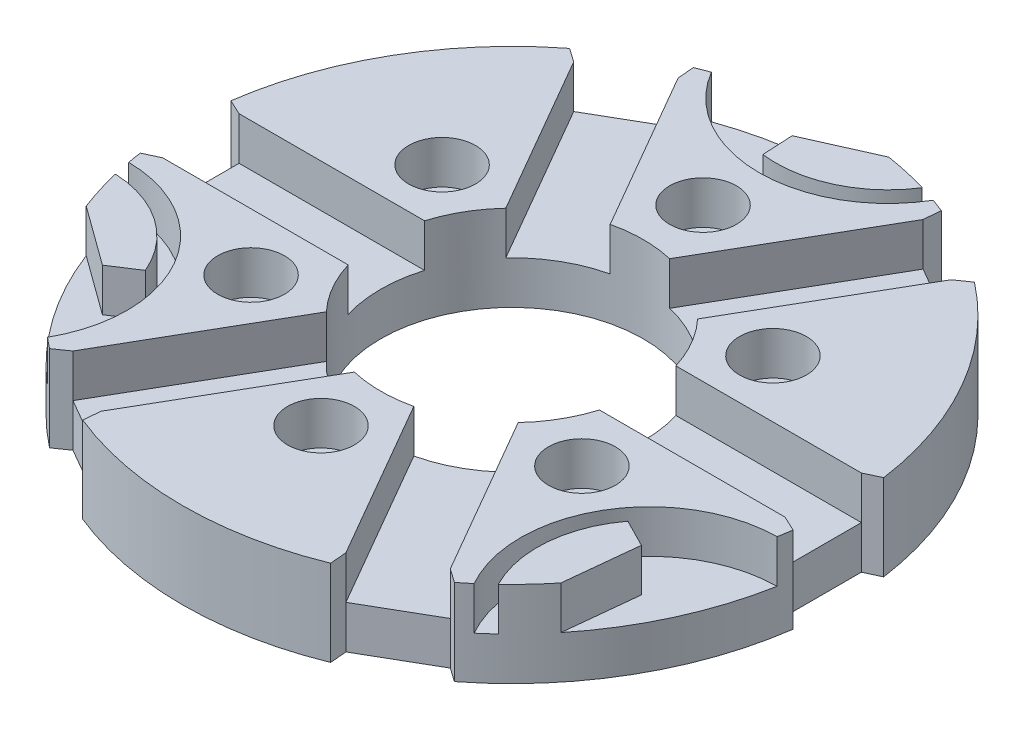
SolidWorks part; units mm, degrees
ref_plane "Front Plane" through (0, 0, 0) normal (0, 0, 1) x (1, 0, 0)
ref_plane "Top Plane" through (0, 0, 0) normal (0, 1, 0) x (1, 0, 0)
ref_plane "Right Plane" through (0, 0, 0) normal (1, 0, 0) x (0, 0, -1)
sketch "Sketch1" plane through (0, 0, 0) normal (0, 1, 0) x (1, 0, 0)
  line L0 (69, 0) -> (-69, 0) construction
  line L1 (0, -69) -> (0, 69) construction
  line L2 (0, 0) -> (34.5, -59.7558) construction
  line L3 (0, 0) -> (59.7558, -34.5) construction
  line L4 (24, -41.5692) -> (26.8492, -74.1354) construction
  line L5 (24, -41.5692) -> (53.9114, -62.5134) construction
  line L6 (29.3432, -66.8239) -> (28.2613, -64.9501)
  line L7 (20.0835, -18.7857) -> (39.5062, -52.4268)
  line L8 (25.6498, -60.4268) -> (25.9565, -63.9317)
  line L9 (39.5062, -52.4268) -> (42.3882, -54.4448)
  line L10 (25.6498, -60.4268) -> (39.5062, -52.4268)
  line L11 (25.6498, -60.4268) -> (6.2271, -26.7857)
  line L12 (-6.2271, -26.7857) -> (-25.6498, -60.4268)
  line L13 (-39.5062, -52.4268) -> (-25.6498, -60.4268)
  line L14 (-39.5062, -52.4268) -> (-20.0835, -18.7857)
  line L15 (0, 0) -> (-34.5, -59.7558) construction
  line L16 (-39.5062, -52.4268) -> (-42.3882, -54.4448)
  line L17 (-25.6498, -60.4268) -> (-25.9565, -63.9317)
  line L18 (-26.3106, -8) -> (-65.1561, -8)
  line L19 (-65.1561, 8) -> (-65.1561, -8)
  line L20 (-65.1561, 8) -> (-26.3106, 8)
  line L21 (0, 0) -> (-69, 0) construction
  line L22 (-65.1561, 8) -> (-68.3447, 9.4869)
  line L23 (-65.1561, -8) -> (-68.3447, -9.4869)
  line L24 (-20.0835, 18.7857) -> (-39.5062, 52.4268)
  line L25 (-25.6498, 60.4268) -> (-39.5062, 52.4268)
  line L26 (-25.6498, 60.4268) -> (-6.2271, 26.7857)
  line L27 (0, 0) -> (-34.5, 59.7558) construction
  line L28 (-25.6498, 60.4268) -> (-25.9565, 63.9317)
  line L29 (-39.5062, 52.4268) -> (-42.3882, 54.4448)
  line L30 (6.2271, 26.7857) -> (25.6498, 60.4268)
  line L31 (39.5062, 52.4268) -> (25.6498, 60.4268)
  line L32 (39.5062, 52.4268) -> (20.0835, 18.7857)
  line L33 (0, 0) -> (34.5, 59.7558) construction
  line L34 (39.5062, 52.4268) -> (42.3882, 54.4448)
  line L35 (25.6498, 60.4268) -> (25.9565, 63.9317)
  line L36 (26.3106, 8) -> (65.1561, 8)
  line L37 (65.1561, -8) -> (65.1561, 8)
  line L38 (65.1561, -8) -> (26.3106, -8)
  line L39 (0, 0) -> (69, 0) construction
  line L40 (65.1561, -8) -> (68.3447, -9.4869)
  line L41 (65.1561, 8) -> (68.3447, 9.4869)
  arc A0 (42.3882, -54.4448) -> (68.3447, -9.4869) centre (0, 0) ccw
  circle A1 centre (0, 0) radius 27.5
  circle A2 centre (0, 0) radius 48 construction
  arc A3 (-42.3882, 54.4448) -> (-68.3447, 9.4869) centre (0, 0) ccw
  arc A4 (25.9565, 63.9317) -> (-25.9565, 63.9317) centre (0, 0) ccw
  arc A5 (68.3447, 9.4869) -> (42.3882, 54.4448) centre (0, 0) ccw
  arc A6 (-25.9565, -63.9317) -> (25.9565, -63.9317) centre (0, 0) ccw
  arc A7 (-68.3447, -9.4869) -> (-42.3882, -54.4448) centre (0, 0) ccw
  point P1 (0, 0)
  point P59 (0, 0)
  dimension "D1" = 138
  dimension "D2" = 55
  dimension "D5" = 96
  dimension "D6" = 50
  dimension "D3" = 30
  dimension "D4" = 30
  dimension "D7" = 25
  dimension "D8" = 8
  dimension "D9" = 6
extrude "Boss-Extrude2" add sketch "Sketch1" along normal blind 18 contours L35 A4 L28 L26 A1 L30 | L41 A5 L34 L32 A1 L36 | A1 L7 L9 A0 L40 L38 | L17 A6 L8 L11 A1 L12 | L23 A7 L16 L14 A1 L18 | L29 A3 L22 L20 A1 L24 region at (44.4985, 0, 25.6912) region at (0, 0, 51.3824) region at (-44.4985, 0, 25.6912) region at (44.4985, 0, -25.6912) region at (-44.4985, 0, -25.6912) region at (0, 0, -51.3824)
extrude "Boss-Extrude3" add sketch "Sketch1<3>" along normal blind 9 contours A1 L32 L31 L30 | A1 L26 L25 L24 | A1 L20 L19 L18 | A1 L14 L13 L12 | A1 L38 L37 L36 | A1 L11 L10 L7 region at (23.065, 0, 39.9497) region at (46.1299, 0, 0) region at (-23.065, 0, 39.9497) region at (-46.1299, 0, 0) region at (23.065, 0, -39.9497) region at (-23.065, 0, -39.9497)
sketch "Sketch1<3>" plane through (0, 0, 0) normal (0, 1, 0) x (1, 0, 0) same geometry as "Sketch1"
sketch "Sketch2" plane through (0, 18, 0) normal (0, 1, 0) x (1, 0, 0)
  line L0 (69, 0) -> (-69, 0) construction
  circle A0 centre (0, 0) radius 40 construction
  circle A1 centre (0, 40) radius 4.5
  circle A2 centre (0, 40) radius 7
  circle A3 centre (34.641, 20) radius 7
  circle A4 centre (34.641, 20) radius 4.5
  circle A5 centre (34.641, -20) radius 7
  circle A6 centre (34.641, -20) radius 4.5
  circle A7 centre (0, -40) radius 7
  circle A8 centre (0, -40) radius 4.5
  circle A9 centre (-34.641, -20) radius 7
  circle A10 centre (-34.641, -20) radius 4.5
  circle A11 centre (-34.641, 20) radius 7
  circle A12 centre (-34.641, 20) radius 4.5
  point P7 (0, 0)
  point P8 (0, 0)
  point P25 (0, 0)
  dimension "D1" = 80
  dimension "D2" = 9
  dimension "D3" = 14
  dimension "D4" = 6
extrude "Cut-Extrude1" cut sketch "Sketch2" against normal blind 9
extrude "Cut-Extrude2" cut sketch "Sketch2<3>" against normal blind 18 contours A4 | A6 | A1 | A8 | A10 | A12
sketch "Sketch2<3>" plane through (0, 18, 0) normal (0, 1, 0) x (1, 0, 0) same geometry as "Sketch2"
sketch "Sketch6" plane through (0, 18, 0) normal (0, 1, 0) x (1, 0, 0)
  line L0 (0, 0) -> (-68.1995, -39.375) construction
  line L1 (-51.9976, -33.7676) -> (-46.5515, -30.2309)
  line L2 (-51.9976, -33.7676) -> (-64.408, -24.7509)
  line L3 (0, -69) -> (0, 69) construction
  line L4 (-3.2448, 61.915) -> (-2.905, 55.4302)
  line L5 (-3.2448, 61.915) -> (10.7691, 68.1544)
  line L6 (55.2424, -28.1474) -> (49.4565, -25.1993)
  line L7 (55.2424, -28.1474) -> (53.6389, -43.4035)
  arc A0 (-67.8809, -12.3769) -> (-44.6591, -52.5981) centre (0, 0) ccw construction
  arc A1 (-46.5515, -30.2309) -> (-67.1434, -15.8987) centre (-68.1995, -39.375) ccw
  arc A2 (-44.6591, -52.5981) -> (-67.8809, -12.3769) centre (-68.1995, -39.375) ccw
  circle A3 centre (0, 0) radius 62 construction
  arc A4 (-2.905, 55.4302) -> (19.803, 66.0972) centre (0, 78.75) ccw
  arc A5 (-23.2217, 64.975) -> (23.2217, 64.975) centre (0, 78.75) ccw
  arc A6 (49.4565, -25.1993) -> (47.3404, -50.1985) centre (68.1995, -39.375) ccw
  arc A7 (67.8809, -12.3769) -> (44.6591, -52.5981) centre (68.1995, -39.375) ccw
  arc A8 (-67.8809, -12.3769) -> (-44.6591, -52.5981) centre (0, 0) ccw
  arc A9 (23.2217, 64.975) -> (-23.2217, 64.975) centre (0, 0) ccw construction
  arc A10 (23.2217, 64.975) -> (-23.2217, 64.975) centre (0, 0) ccw
  arc A11 (44.6591, -52.5981) -> (67.8809, -12.3769) centre (0, 0) ccw construction
  arc A12 (44.6591, -52.5981) -> (67.8809, -12.3769) centre (0, 0) ccw
  point P33 (0, 0)
  point P36 (0, 0)
  arc M23 (25.9565, 63.9317) -> (-25.9565, 63.9317) centre (0, 0) ccw
  dimension "D2" = 54
  dimension "D3" = 47
  dimension "D4" = 138
  dimension "D5" = 124
  dimension "D1" = 78.75
  dimension "D6" = 3
  dimension "D7" = 66
  dimension "D8" = 3
extrude "Cut-Extrude3" cut sketch "Sketch6" against normal blind 9 contours A5 A4 L4 L5 M23 | A2 A8 A1 L1 L2 | A7 A12 A6 L6 L7 region at (-51.027, 18, 33.4318) region at (-3.4393, 18, -60.9066) region at (54.4663, 18, 27.4747)
